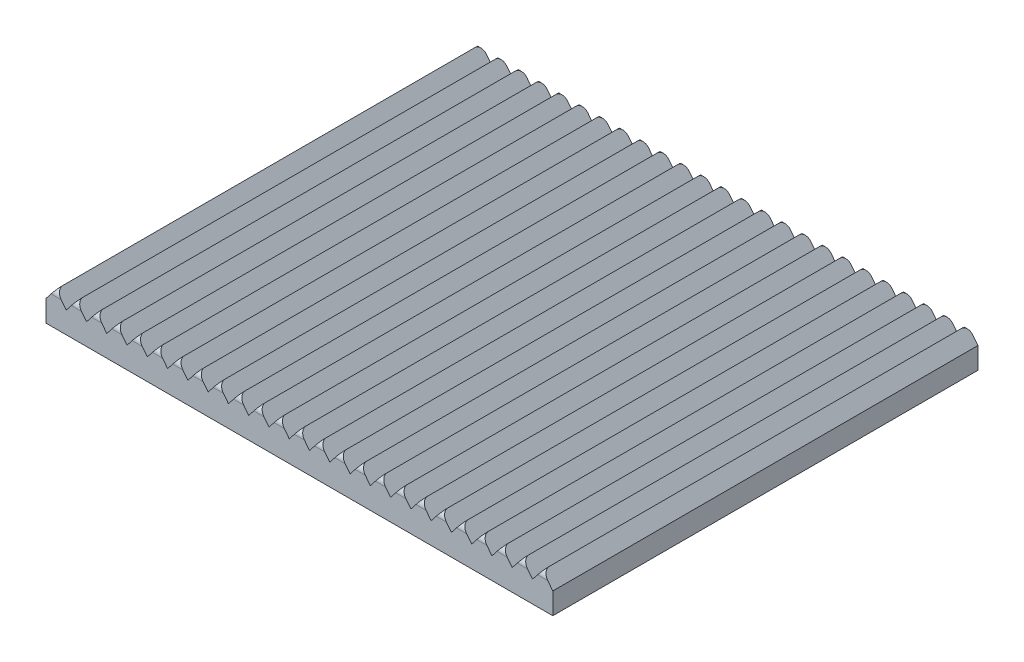
SolidWorks part; units mm, degrees
ref_plane "Front Plane" through (0, 0, 0) normal (0, 0, 1) x (1, 0, 0)
ref_plane "Top Plane" through (0, 0, 0) normal (0, 1, 0) x (1, 0, 0)
ref_plane "Right Plane" through (0, 0, 0) normal (1, 0, 0) x (0, 0, -1)
sketch "Sketch1" plane through (0, 0, 0) normal (0, 1, 0) x (1, 0, 0)
  line L6 (-29.5, 24.75) -> (29.5, 24.75)
  line L28 (-29.5, 24.75) -> (-29.5, -24.75)
  line L29 (-29.5, -24.75) -> (29.5, -24.75)
  line L30 (29.5, 24.75) -> (29.5, -24.75)
  line L31 (-29.5, 24.75) -> (29.5, -24.75) construction
  line L32 (-29.5, -24.75) -> (29.5, 24.75) construction
  circle A1 centre (0, 0) radius 3
  point P0 (0, 0)
  dimension "D3" = 6
  dimension "D1" = 59
  dimension "D2" = 49.5
extrude "Boss-Extrude1" add sketch "Sketch1" along normal blind 1.5
sketch "Sketch2" plane through (0, 0, -24.75) normal (0, 0, -1) x (-1, 0, 0)
  line L0 (-29.5, 1.5) -> (-29.5, 0) construction
  line L1 (-29.5, 1.5) -> (29.5, 1.5)
  line L2 (-29.5, 1.5) -> (-29.5, 2.5)
  line L4 (29.5, 1.5) -> (29.5, 2.5)
  line L5 (-1.18, 2.5) -> (0, 4)
  line L6 (0, 55) -> (0, -55) construction
  line L7 (1.18, 2.5) -> (0, 4)
  line L8 (1.18, 2.5) -> (2.36, 4)
  line L9 (3.54, 2.5) -> (2.36, 4)
  line L10 (3.54, 2.5) -> (4.72, 4)
  line L11 (5.9, 2.5) -> (4.72, 4)
  line L12 (5.9, 2.5) -> (7.08, 4)
  line L13 (8.26, 2.5) -> (7.08, 4)
  line L14 (8.26, 2.5) -> (9.44, 4)
  line L15 (10.62, 2.5) -> (9.44, 4)
  line L16 (10.62, 2.5) -> (11.8, 4)
  line L17 (12.98, 2.5) -> (11.8, 4)
  line L18 (12.98, 2.5) -> (14.16, 4)
  line L19 (15.34, 2.5) -> (14.16, 4)
  line L20 (15.34, 2.5) -> (16.52, 4)
  line L21 (17.7, 2.5) -> (16.52, 4)
  line L22 (17.7, 2.5) -> (18.88, 4)
  line L23 (20.06, 2.5) -> (18.88, 4)
  line L24 (20.06, 2.5) -> (21.24, 4)
  line L25 (22.42, 2.5) -> (21.24, 4)
  line L26 (22.42, 2.5) -> (23.6, 4)
  line L27 (24.78, 2.5) -> (23.6, 4)
  line L28 (24.78, 2.5) -> (25.96, 4)
  line L29 (27.14, 2.5) -> (25.96, 4)
  line L30 (27.14, 2.5) -> (28.32, 4)
  line L31 (29.5, 2.5) -> (28.32, 4)
  line L32 (-29.5, 2.5) -> (-28.32, 4)
  line L33 (-27.14, 2.5) -> (-28.32, 4)
  line L34 (-27.14, 2.5) -> (-25.96, 4)
  line L35 (-24.78, 2.5) -> (-25.96, 4)
  line L36 (-24.78, 2.5) -> (-23.6, 4)
  line L37 (-22.42, 2.5) -> (-23.6, 4)
  line L38 (-22.42, 2.5) -> (-21.24, 4)
  line L39 (-20.06, 2.5) -> (-21.24, 4)
  line L40 (-20.06, 2.5) -> (-18.88, 4)
  line L41 (-17.7, 2.5) -> (-18.88, 4)
  line L42 (-17.7, 2.5) -> (-16.52, 4)
  line L43 (-15.34, 2.5) -> (-16.52, 4)
  line L44 (-15.34, 2.5) -> (-14.16, 4)
  line L45 (-12.98, 2.5) -> (-14.16, 4)
  line L46 (-12.98, 2.5) -> (-11.8, 4)
  line L47 (-10.62, 2.5) -> (-11.8, 4)
  line L48 (-10.62, 2.5) -> (-9.44, 4)
  line L49 (-8.26, 2.5) -> (-9.44, 4)
  line L50 (-8.26, 2.5) -> (-7.08, 4)
  line L51 (-5.9, 2.5) -> (-7.08, 4)
  line L52 (-5.9, 2.5) -> (-4.72, 4)
  line L53 (-3.54, 2.5) -> (-4.72, 4)
  line L54 (-3.54, 2.5) -> (-2.36, 4)
  line L55 (-1.18, 2.5) -> (-2.36, 4)
  dimension "D1" = 1
  dimension "D2" = 1.5
  dimension "D3" = 13
extrude "Boss-Extrude2" add sketch "Sketch2" against normal up to surface (49.5 mm away) up to face at (0, 0.75, 24.75)
sketch "Sketch3" plane through (0, 0, 0) normal (0, -1, 0) x (-1, 0, 0)
  line L0 (0, 2.2) -> (0, -2.2) construction
  line L2 (-1.75, -2.4367) -> (-1.75, -5)
  line L3 (-1.75, -5) -> (1.75, -5)
  line L4 (1.75, -2.4367) -> (1.75, -5)
  arc A0 (1.75, -2.4367) -> (-1.75, -2.4367) centre (0, 0) ccw
  dimension "D2" = 6
  dimension "D1" = 3.5
  dimension "D3" = 5
  dimension "D4" = 1.75
extrude "Cut-Extrude1" cut sketch "Sketch3" against normal blind 2
sketch "Sketch4" plane through (29.5, 0, 0) normal (1, 0, 0) x (0, 0, -1)
  line L1 (-24.75, 4) -> (-24.75, 2.5) construction
  line L2 (-24.75, 4) -> (24.75, 4) construction
  line L3 (-24, 4) -> (-24.75, 4)
  line L4 (-24.75, 4) -> (-24.75, 3.25)
  arc A0 (-24.75, 3.25) -> (-24, 4) centre (-24, 3.25) cw
extrude "Cut-Extrude3" cut sketch "Sketch4" against normal through all
mirror "Mirror1" about plane through (0, 0, 0) normal (0, 0, 1) of "Cut-Extrude3"
chamfer "Chamfer3" distance 2 angle 45 1 edges at (0, 0, 5)
